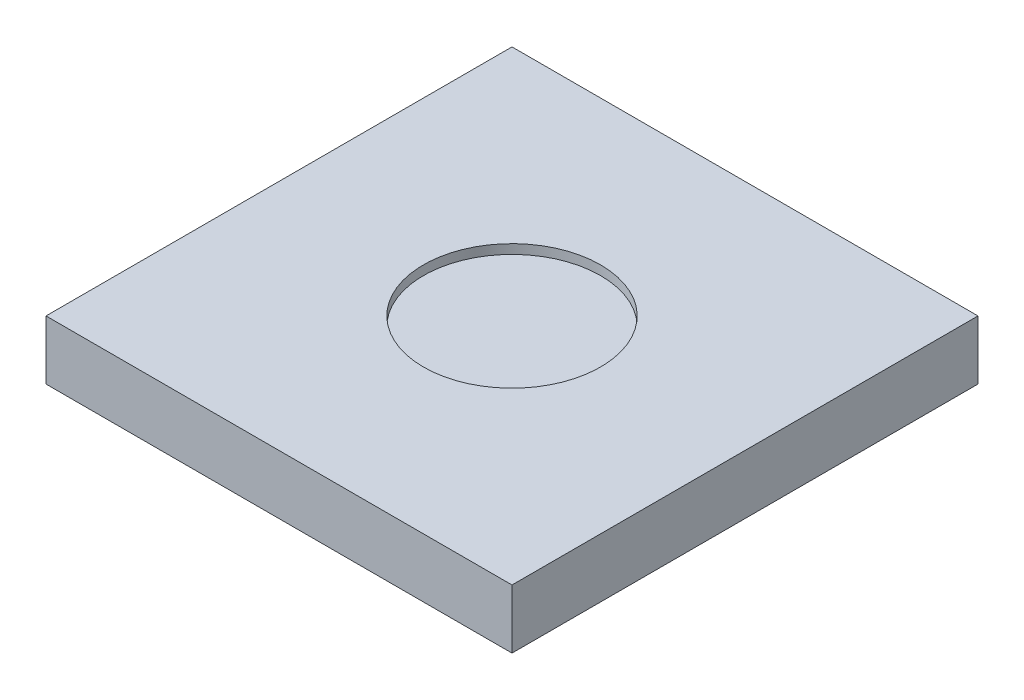
SolidWorks part; units mm, degrees
ref_plane "Front Plane" through (0, 0, 0) normal (0, 0, 1) x (1, 0, 0)
ref_plane "Top Plane" through (0, 0, 0) normal (0, 1, 0) x (1, 0, 0)
ref_plane "Right Plane" through (0, 0, 0) normal (1, 0, 0) x (0, 0, -1)
sketch "Sketch1" plane through (0, 0, 0) normal (0, 1, 0) x (1, 0, 0)
  line L1 (0, 0) -> (150, 0)
  line L2 (0, 0) -> (0, 150)
  line L3 (0, 150) -> (150, 150)
  line L4 (150, 0) -> (150, 150)
  dimension "D1" = 150
  dimension "D2" = 150
extrude "Boss-Extrude1" add sketch "Sketch1" along normal blind 19
ref_plane "Plane1" through (105, 0, 0) normal (1, 0, 0) x (0, 0, -1)
sketch "Sketch2" plane through (0, 19, 0) normal (0, 1, 0) x (1, 0, 0)
  line L0 (75, 150) -> (75, 0) construction
  line L1 (150, 150) -> (0, 150) construction
  line L2 (0, 0) -> (150, 0) construction
  circle A0 centre (75, 75) radius 28.5
  dimension "D1" = 57
extrude "Cut-Extrude1" cut sketch "Sketch2" against normal blind 3
ref_point "Point1"
ref_axis "Axis1" through (75, 16, -75) along (0, 1, 0)
